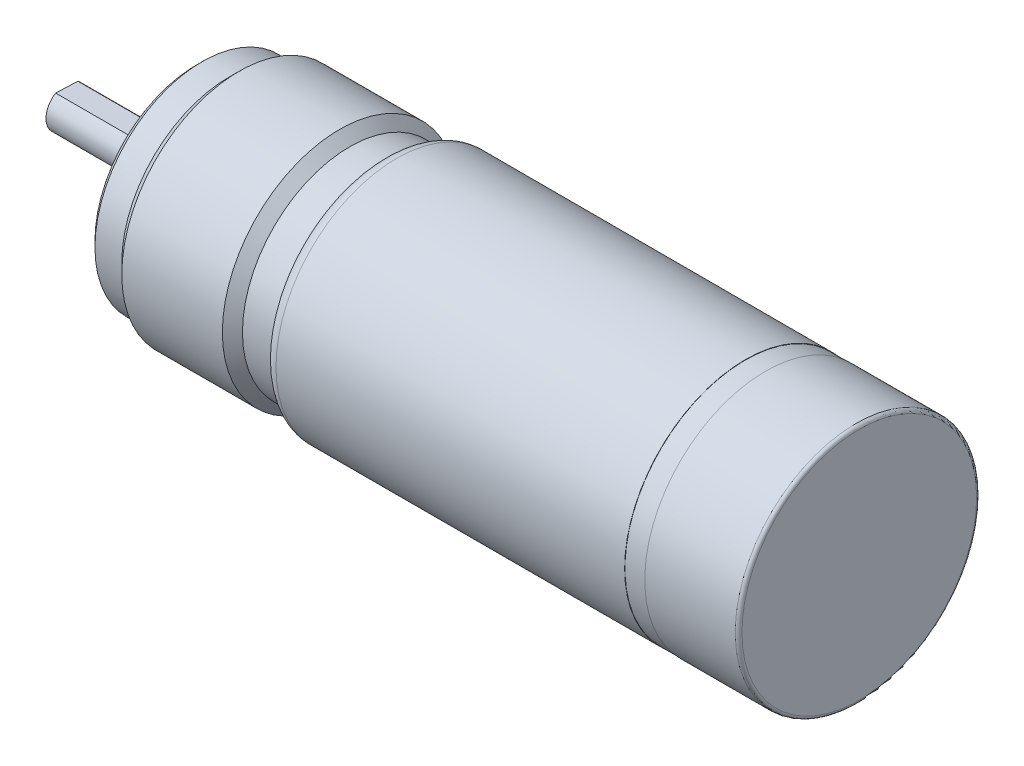
SolidWorks part; units mm, degrees
ref_plane "Спереди" through (0, 0, 0) normal (0, 0, 1) x (1, 0, 0)
ref_plane "Сверху" through (0, 0, 0) normal (0, 1, 0) x (1, 0, 0)
ref_plane "Справа" through (0, 0, 0) normal (1, 0, 0) x (0, 0, -1)
sketch "Эскиз1" plane through (0, 0, 0) normal (0, 1, 0) x (1, 0, 0)
  line L0 (0, 0) -> (104.9, 0) construction
  line L1 (24.3, 16) -> (25.8, 17.5)
  line L2 (0, 0) -> (16.3, 0)
  line L3 (0, 0) -> (0, 3)
  line L4 (0, 3) -> (16.3, 3)
  line L5 (16.3, 0) -> (16.3, 3)
  line L6 (16.3, 0) -> (19.3, 0)
  line L7 (16.3, 0) -> (16.3, 10)
  line L8 (16.3, 10) -> (19.3, 10)
  line L9 (19.3, 0) -> (19.3, 10)
  line L10 (19.3, 0) -> (24.3, 0)
  line L11 (19.3, 0) -> (19.3, 15)
  line L12 (20.3, 16) -> (24.3, 16)
  line L13 (24.3, 0) -> (24.3, 16)
  line L14 (24.3, 0) -> (42.3, 0)
  line L15 (24.3, 0) -> (24.3, 16)
  line L16 (25.8, 17.5) -> (40.8, 17.5)
  line L17 (42.3, 0) -> (42.3, 16)
  line L18 (19.3, 15) -> (20.3, 16)
  line L19 (40.8, 17.5) -> (42.3, 16)
  line L21 (42.3, 0) -> (47.3, 0)
  line L22 (42.3, 0) -> (42.3, 16)
  line L23 (42.3, 16) -> (47.3, 16)
  line L24 (47.3, 0) -> (47.3, 16)
  line L25 (47.3, 0) -> (104.3, 0)
  line L26 (47.3, 0) -> (47.3, 16)
  line L27 (49.3, 18) -> (104.3, 18)
  line L28 (104.3, 0) -> (104.3, 18)
  arc A0 (47.3, 16) -> (49.3, 18) centre (49.3, 16) cw
  point P10 (19.3, 16)
  point P12 (42.3, 17.5)
  point P13 (24.3, 17.5)
  point P28 (47.3, 18)
  dimension "D14" = 2
  dimension "D2" = 3
  dimension "D3" = 16.3
  dimension "D4" = 3
  dimension "D5" = 10
  dimension "D6" = 16
  dimension "D7" = 5
  dimension "D8" = 17.5
  dimension "D9" = 18
  dimension "D10" = 5
  dimension "D11" = 18
  dimension "D12" = 57
  dimension "D15" = 104.3
  dimension "D16" = 31
  dimension "D17" = 88
revolve "Повернуть1 основной корпус" add sketch "Эскиз1" angle 360 about L0 region at (21.8136, 0, -7.9518) region at (33.3, 0, -8.6906) region at (17.8, 0, -5) region at (44.8, 0, -8) region at (8.15, 0, -1.5) region at (75.8235, 0, -8.9928)
sketch "Эскиз19" plane through (0, 0, 0) normal (0, 1, 0) x (1, 0, 0)
  line L0 (103.0047, 0) -> (0, 0) construction
  line L1 (104.3, 18) -> (101.3, 18)
  line L2 (104.3, 18) -> (104.3, 17.95)
  line L3 (104.3, 17.95) -> (101.3, 17.95)
  line L4 (101.3, 18) -> (101.3, 17.95)
  dimension "D1" = 3
  dimension "D2" = 0.05
revolve "Вырез-Повернуть2 пластиковая часть" cut sketch "Эскиз19" angle 360 about L0
sketch "Эскиз20" plane through (104.3, 0, 0) normal (1, 0, 0) x (0, 0, -1)
  circle A0 centre (0, 0) radius 18
  dimension "D1" = 36
extrude "Бобышка-Вытянуть2 пластиковая крышка контактов" add sketch "Эскиз20" along normal blind 14
sketch "Эскиз11" plane through (16.3, 0, 0) normal (-1, 0, 0) x (0, 0, 1)
  line L0 (-4.3589, 9) -> (4.3589, 9)
  line L1 (4.3589, -9) -> (-4.3589, -9)
  circle A0 centre (0, 0) radius 10 construction
  circle A3 centre (0, 0) radius 10
  circle M1 centre (0, 0) radius 10
  dimension "D1" = 18
  dimension "D2" = 9
extrude "Вырез-Вытянуть6" cut sketch "Эскиз11" against normal blind 3 contours L0 M1 | L1 M1 region at (16.3, 9.4018, 0) region at (16.3, -9.4018, 0)
sketch "Эскиз6" plane through (0, 0, 0) normal (-1, 0, 0) x (0, 0, 1)
  line L0 (1.5611, 2.5618) -> (-1.7531, 2.4345)
  circle A0 centre (0, 0) radius 3
  circle M1 centre (0, 0) radius 3
  dimension "D2" = 6
  dimension "D1" = 2.5
extrude "Вырез-Вытянуть4 на оси" cut sketch "Эскиз6" against normal blind 12 contours L0 M1 region at (0, 2.6995, -0.1037)
sketch "Эскиз13" plane through (19.3, 0, 0) normal (-1, 0, 0) x (0, 0, 1)
  line L0 (0, 0) -> (-9.1924, 9.1924)
  circle A0 centre (0, 0) radius 13
  circle A2 centre (-9.1924, 9.1924) radius 1.5
  dimension "D1" = 26
  dimension "D2" = 3
extrude "Вырез-Вытянуть8 для винтов" cut sketch "Эскиз13" against normal blind 7 contours A0 A2 | L0 A2 A0 | A0 A2 L0 region at (19.3, 8.2899, -9.1729) region at (19.3, 9.1729, -8.2899) region at (19.3, 9.6313, -9.6313)
pattern_circular "Круговой массив2 для винтов" count 4 every 90 about axis through (0, 0, 0) along (-1, 0, 0) of face at (26.3, 9.1924, -7.6924) of face at (26.3, 9.1924, -7.6924)
fillet "Скругление1" radius 0.5 16 edges at (19.3, 0, 10) (19.3, 0, -10) (19.3, 0, 15) (19.3, 9.1924, -7.6924) (19.3, -7.6924, -9.1924) (19.3, -9.1924, 7.6924) (19.3, 7.6924, 9.1924) (17.8, 9, -4.3589) (19.3, 9, 0) (17.8, 9, 4.3589) (16.3, 9, 0) (17.8, -9, 4.3589) (19.3, -9, 0) (17.8, -9, -4.3589) (16.3, -9, 0) (118.3, 0, -18)
